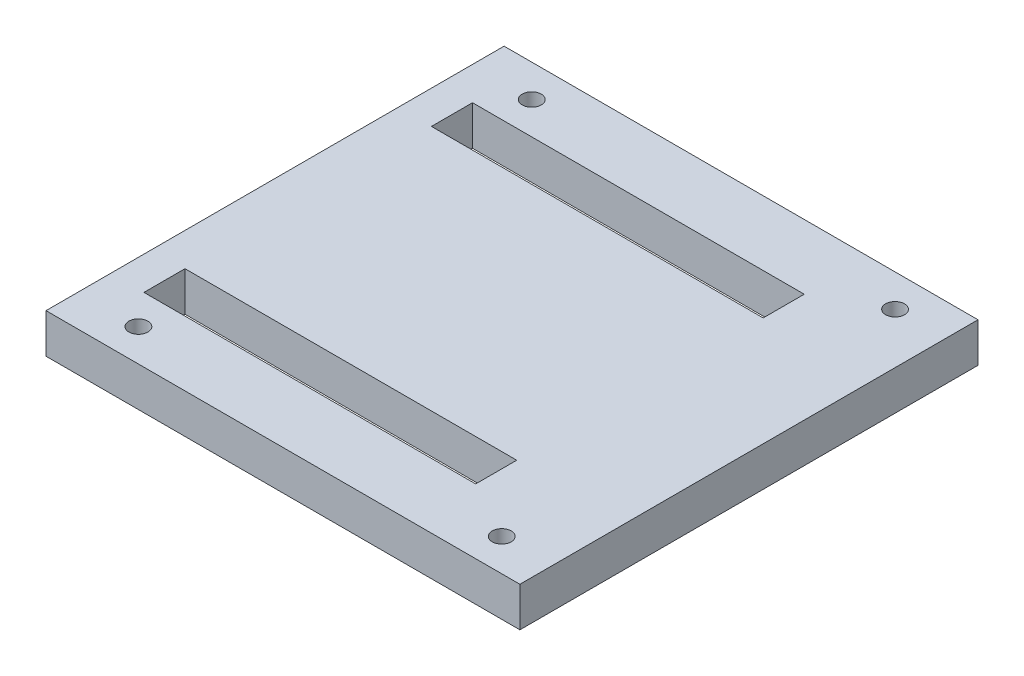
SolidWorks part; units mm, degrees
ref_plane "前视基准面" through (0, 0, 0) normal (0, 0, 1) x (1, 0, 0)
ref_plane "上视基准面" through (0, 0, 0) normal (0, 1, 0) x (1, 0, 0)
ref_plane "右视基准面" through (0, 0, 0) normal (1, 0, 0) x (0, 0, -1)
other "Configuration Table"
sketch "草图1" plane through (0, 0, 0) normal (0, 1, 0) x (1, 0, 0)
  line L1 (-15, -14.5) -> (15, -14.5)
  line L2 (-15, -14.5) -> (-15, 14.5)
  line L3 (-15, 14.5) -> (15, 14.5)
  line L4 (15, -14.5) -> (15, 14.5)
  line L5 (-15, -14.5) -> (15, 14.5) construction
  line L6 (-15, 14.5) -> (15, -14.5) construction
  line L7 (-12.9, 10.4) -> (8.1, 10.4)
  line L8 (-12.9, 10.4) -> (-12.9, 7.8)
  line L9 (-12.9, 7.8) -> (8.1, 7.8)
  line L10 (8.1, 10.4) -> (8.1, 7.8)
  line L11 (-12.9, -7.8) -> (8.1, -7.8)
  line L12 (-12.9, -7.8) -> (-12.9, -10.4)
  line L13 (-12.9, -10.4) -> (8.1, -10.4)
  line L14 (8.1, -7.8) -> (8.1, -10.4)
  point P0 (0, 0)
  point P7 (0, 0)
  dimension "D1" = 29
  dimension "D2" = 30
  dimension "D3" = 2.6
  dimension "D4" = 21
  dimension "D5" = 15.6
  dimension "D6" = 7.8
  dimension "D7" = 2.1
extrude "凸台-拉伸1" add sketch "草图1" along normal blind 2.5
sketch "草图2" plane through (0, 0, 0) normal (0, -1, 0) x (1, 0, 0)
  circle A0 centre (-11.2, -12.45) radius 1
  circle A1 centre (-11.2, -12.45) radius 0.6
  circle A2 centre (-11.2, 12.45) radius 1
  circle A3 centre (-11.2, 12.45) radius 0.6
  circle A4 centre (11.8, 12.45) radius 1
  circle A5 centre (11.8, 12.45) radius 0.6
  circle A6 centre (11.8, -12.45) radius 1
  circle A7 centre (11.8, -12.45) radius 0.6
  point P12 (0, 0)
  dimension "D1" = 1.2
  dimension "D2" = 2
extrude "切除-拉伸1" cut sketch "草图2" against normal through all contours A5 | A7 | A1 | A3
extrude "切除-拉伸2" cut sketch "草图2<3>" against normal blind 1.5
sketch "草图2<3>" plane through (0, 0, 0) normal (0, -1, 0) x (1, 0, 0) same geometry as "草图2"
